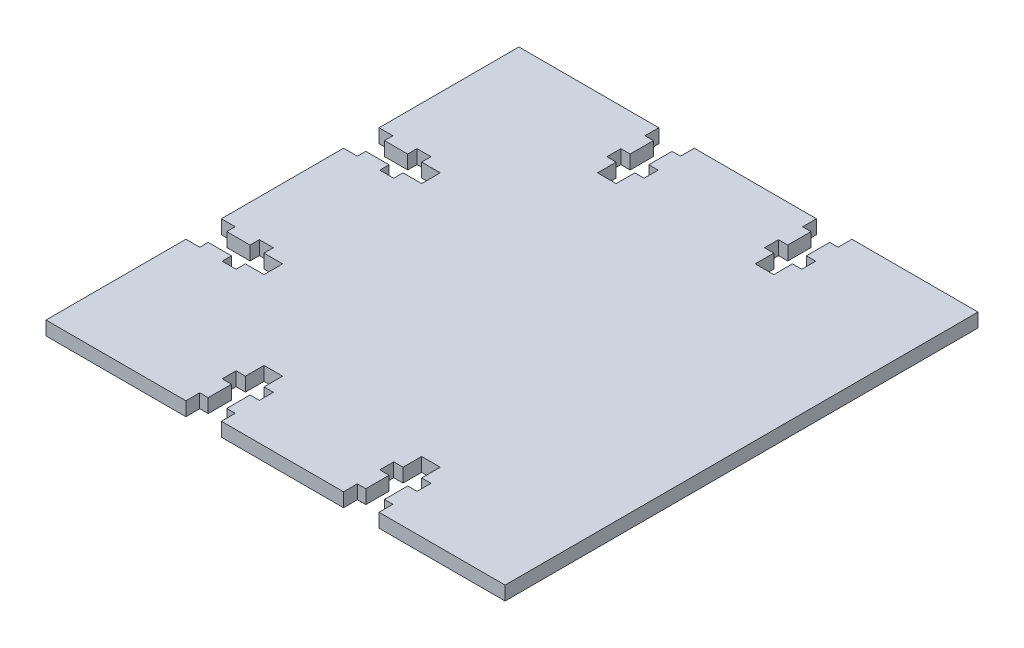
SolidWorks part; units mm, degrees
ref_plane "前视基准面" through (0, 0, 0) normal (0, 0, 1) x (1, 0, 0)
ref_plane "上视基准面" through (0, 0, 0) normal (0, 1, 0) x (1, 0, 0)
ref_plane "右视基准面" through (0, 0, 0) normal (1, 0, 0) x (0, 0, -1)
sketch "草图1" plane through (0, 0, 0) normal (0, 1, 0) x (1, 0, 0)
  line L0 (0, 50.8) -> (101.6, 50.8) construction
  line L1 (0, 0) -> (101.6, 0)
  line L2 (0, 0) -> (0, 101.6)
  line L3 (0, 101.6) -> (101.6, 101.6)
  line L4 (101.6, 0) -> (101.6, 101.6)
  line L5 (33.8667, 101.6) -> (33.8667, 0) construction
  line L6 (30.0567, 101.6) -> (30.0567, 98.6282)
  line L7 (30.0567, 98.6282) -> (31.8667, 98.6282)
  line L8 (31.8667, 98.6282) -> (31.8667, 93.6282)
  line L9 (31.8667, 93.6282) -> (29.8667, 93.6282)
  line L10 (29.8667, 93.6282) -> (29.8667, 90.6282)
  line L11 (29.8667, 90.6282) -> (31.8667, 90.6282)
  line L12 (31.8667, 90.6282) -> (31.8667, 86.6282)
  line L13 (31.8667, 86.6282) -> (35.8667, 86.6282)
  line L14 (37.8667, 90.6282) -> (35.8667, 90.6282)
  line L15 (35.8667, 90.6282) -> (35.8667, 86.6282)
  line L16 (37.8667, 93.6282) -> (37.8667, 90.6282)
  line L17 (35.8667, 93.6282) -> (37.8667, 93.6282)
  line L18 (35.8667, 98.6282) -> (35.8667, 93.6282)
  line L19 (37.6767, 98.6282) -> (35.8667, 98.6282)
  line L20 (37.6767, 101.6) -> (37.6767, 98.6282)
  line L21 (50.8, 101.6) -> (50.8, -1.3557) construction
  line L22 (101.6, 0) -> (0, 101.6) construction
  line L23 (0, 71.5433) -> (2.9718, 71.5433)
  line L24 (2.9718, 71.5433) -> (2.9718, 69.7333)
  line L25 (2.9718, 69.7333) -> (7.9718, 69.7333)
  line L26 (7.9718, 69.7333) -> (7.9718, 71.7333)
  line L27 (7.9718, 71.7333) -> (10.9718, 71.7333)
  line L28 (10.9718, 71.7333) -> (10.9718, 69.7333)
  line L29 (10.9718, 69.7333) -> (14.9718, 69.7333)
  line L30 (14.9718, 69.7333) -> (14.9718, 65.7333)
  line L31 (10.9718, 65.7333) -> (14.9718, 65.7333)
  line L32 (10.9718, 63.7333) -> (10.9718, 65.7333)
  line L33 (7.9718, 63.7333) -> (10.9718, 63.7333)
  line L34 (7.9718, 65.7333) -> (7.9718, 63.7333)
  line L35 (2.9718, 65.7333) -> (7.9718, 65.7333)
  line L36 (2.9718, 63.9233) -> (2.9718, 65.7333)
  line L37 (0, 63.9233) -> (2.9718, 63.9233)
  point P19 (33.8667, 86.6282)
  dimension "D1" = 101.6
  dimension "D2" = 101.6
  dimension "D3" = 33.8667
  dimension "D4" = 3.81
  dimension "D5" = 2
  dimension "D6" = 2.9718
  dimension "D7" = 5
  dimension "D8" = 3
  dimension "D9" = 2
  dimension "D10" = 2
  dimension "D11" = 4
extrude "凸台-拉伸1" add sketch "草图1" along normal blind 2.9718 contours L3 L20 L19 L18 L17 L16 L14 L15 L13 L12 L11 L10 L9 L8 L7 L6 L2 L1 L4 | L20 L3 L6 L7 L8 L9 L10 L11 L12 L13 L15 L14 L16 L17 L18 L19 | L2 L37 L36 L35 L34 L33 L32 L31 L30 L29 L28 L27 L26 L25 L24 L23 region at (51.2942, 0, -50.3058) region at (6.9932, 0, -67.7333) region at (33.8667, 0, -94.6068)
extrude "切除-拉伸1" cut sketch "草图1<3>" along normal through all contours L20 L3 L6 L7 L8 L9 L10 L11 L12 L13 L15 L14 L16 L17 L18 L19 region at (33.8667, 0, -94.6068)
sketch "草图1<3>" plane through (0, 0, 0) normal (0, 1, 0) x (1, 0, 0) same geometry as "草图1"
ref_plane "基准面1" through (0, 0, -50.8) normal (0, 0, -1) x (-1, 0, 0)
mirror "镜向1" about plane through (0, 0, -50.8) normal (0, 0, -1) of "切除-拉伸1"
ref_plane "基准面2" through (50.8, 0, 0) normal (1, 0, 0) x (0, 0, -1)
mirror "镜向2" about plane through (50.8, 0, 0) normal (1, 0, 0) of "镜向1", "切除-拉伸1"
extrude "切除-拉伸3" cut sketch "草图1<4>" along normal through all contours L2 L37 L36 L35 L34 L33 L32 L31 L30 L29 L28 L27 L26 L25 L24 L23 region at (6.9932, 0, -67.7333)
sketch "草图1<4>" plane through (0, 0, 0) normal (0, 1, 0) x (1, 0, 0) same geometry as "草图1"
mirror "镜向3" about plane through (0, 0, -50.8) normal (0, 0, -1) of "切除-拉伸3"
sketch "草图2" plane through (101.6, 0, 0) normal (1, 0, 0) x (0, 0, -1)
  line L4 (0, 0) -> (101.6, 0)
  line L5 (101.6, 0) -> (101.6, 2.9718)
  line L6 (101.6, 2.9718) -> (0, 2.9718)
  line L7 (0, 2.9718) -> (0, 0)
  line L8 (0, 0) -> (101.6, 0)
  line L9 (101.6, 0) -> (101.6, 2.9718)
  line L10 (101.6, 2.9718) -> (0, 2.9718)
  line L11 (0, 2.9718) -> (0, 0)
  dimension "D1" = 0
extrude "切除-拉伸4" cut sketch "草图2" against normal blind 2.9718
